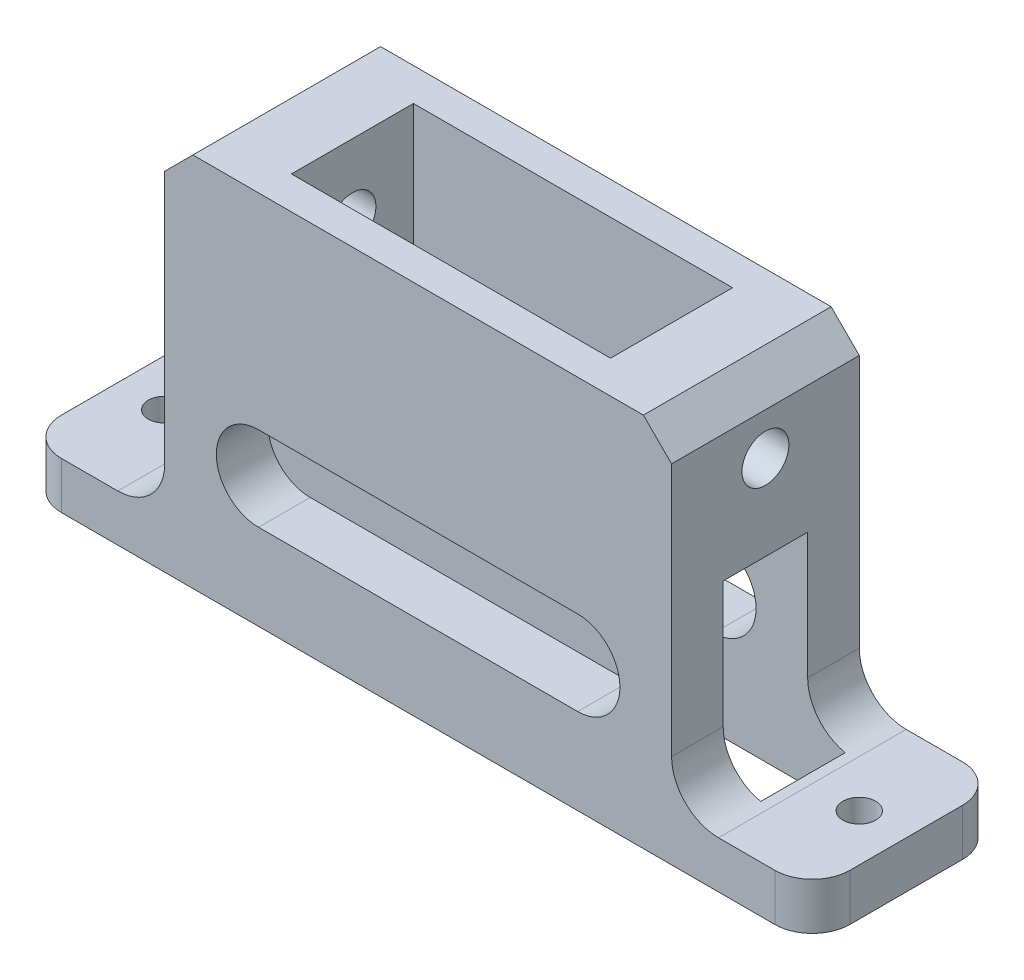
SolidWorks part; units mm, degrees
ref_plane "Front Plane" through (0, 0, 0) normal (0, 0, 1) x (1, 0, 0)
ref_plane "Top Plane" through (0, 0, 0) normal (0, 1, 0) x (1, 0, 0)
ref_plane "Right Plane" through (0, 0, 0) normal (1, 0, 0) x (0, 0, -1)
sketch "Sketch1" plane through (0, 0, 0) normal (0, 1, 0) x (1, 0, 0)
  line L1 (-27, 10) -> (27, 10)
  line L2 (-27, 10) -> (-27, -10)
  line L3 (-27, -10) -> (27, -10)
  line L4 (27, 10) -> (27, -10)
  line L5 (-27, 10) -> (27, -10) construction
  line L6 (-27, -10) -> (27, 10) construction
  point P0 (0, 0)
  dimension "D1" = 20
  dimension "D2" = 54
extrude "Boss-Extrude1" add sketch "Sketch1" along normal blind 40
sketch "Sketch4" plane through (0, 0, 0) normal (0, -1, 0) x (1, 0, 0)
  line L0 (27, -10) -> (-27, -10) construction
  line L1 (-27, 10) -> (-42, 10)
  line L2 (-27, 10) -> (-27, -10)
  line L3 (-27, -10) -> (-42, -10)
  line L4 (-42, 10) -> (-42, -10)
  line L5 (0, -11) -> (0, 11) construction
  line L6 (42, 10) -> (42, -10)
  line L7 (27, -10) -> (42, -10)
  line L8 (27, 10) -> (27, -10)
  line L9 (27, 10) -> (42, 10)
  dimension "D1" = 15
extrude "Boss-Extrude2" add sketch "Sketch4" against normal blind 5
fillet "Fillet1" radius 5 2 edges at (27, 5, 0) (-27, 5, 0)
sketch "Sketch6" plane through (0, 40, 0) normal (0, -1, 0) x (1, 0, 0)
  line L0 (17, 6.5) -> (-17, -6.5) construction
  line L1 (-17, 6.5) -> (17, 6.5)
  line L2 (-17, 6.5) -> (-17, -6.5)
  line L3 (-17, -6.5) -> (17, -6.5)
  line L4 (17, 6.5) -> (17, -6.5)
  line L5 (-27, -10) -> (-27, 10) construction
  dimension "D1" = 10
  dimension "D2" = 13
extrude "Cut-Extrude3" cut sketch "Sketch6" along normal offset from surface (26.35 mm away) 13.65 up to face at (0, 0, 0)
sketch "Sketch7" plane through (0, 0, 10) normal (0, 0, 1) x (1, 0, 0)
  line L0 (-17, 13.65) -> (17, 13.65) construction
  line L4 (-17, 18.15) -> (17, 18.15)
  line L8 (-17, 9.15) -> (17, 9.15)
  line L9 (0, 0) -> (0, 40) construction
  line L10 (-27, 40) -> (27, 40) construction
  line L11 (-17, 13.65) -> (-17, 40) construction
  line L12 (-42, 0) -> (42, 0) construction
  arc A2 (-17, 18.15) -> (-17, 9.15) centre (-17, 13.65) ccw
  arc A3 (17, 9.15) -> (17, 18.15) centre (17, 13.65) ccw
  point P2 (0, 13.65)
  dimension "D1" = 9
  dimension "D2" = 13.65
extrude "Cut-Extrude4" cut sketch "Sketch7" against normal through all
sketch "Sketch3" plane through (-27, 0, 0) normal (-1, 0, 0) x (0, 0, 1)
  line L2 (-10, 32.52) -> (10, 32.52) construction
  line L3 (-10, 40) -> (-10, 10) construction
  line L4 (10, 40) -> (10, 10) construction
  line L6 (10, 0) -> (-10, 0) construction
  line L7 (-10, 40) -> (-10, 10) construction
  line L8 (-10, 13.65) -> (-10, 32.52) construction
  circle A0 centre (0, 32.52) radius 2.5
  dimension "D1" = 5
  dimension "D2" = 13.65
  dimension "D3" = 18.87
extrude "Cut-Extrude2" cut sketch "Sketch3" against normal through all
ref_plane "Plane2" through (0, 0, -4.5) normal (0, 0, -1) x (-1, 0, 0)
sketch "Sketch8" plane through (0, 0, -4.5) normal (0, 0, -1) x (-1, 0, 0)
  line L0 (-17, 13.65) -> (17, 13.65) construction
  line L1 (-17, 27.65) -> (17, 27.65)
  line L3 (31, 13.65) -> (31, 0)
  line L4 (31, 0) -> (-31, 0)
  line L5 (-31, 0) -> (-31, 13.65)
  line L6 (42, 0) -> (-42, 0) construction
  arc A1 (-17, 27.65) -> (-31, 13.65) centre (-17, 13.65) ccw
  arc A3 (31, 13.65) -> (17, 27.65) centre (17, 13.65) ccw
  point P3 (0, 13.65)
  point P8 (0, 13.65)
  point P9 (37.6061, 0)
  point P11 (0, 0)
  point P14 (-31, 13.65)
  point P15 (-31, 13.65)
  point P16 (0, 0)
  point P17 (-31, 13.65)
  point P20 (17, 27.3)
  dimension "D1" = 14
extrude "Cut-Extrude5" cut sketch "Sketch8" against normal blind 9
sketch "Sketch9" plane through (0, 5, 0) normal (0, 1, 0) x (1, 0, 0)
  line L0 (-32, 0) -> (-42, 0) construction
  line L1 (-32, -10) -> (-32, 10) construction
  line L2 (-42, -10) -> (-42, 10) construction
  line L3 (32, 0) -> (42, 0) construction
  line L4 (32, 10) -> (32, -10) construction
  line L5 (42, 10) -> (42, -10) construction
  circle A0 centre (-37, 0) radius 1.75
  circle A1 centre (37, 0) radius 1.75
  dimension "D1" = 3.5
  dimension "D2" = 3.5
extrude "Cut-Extrude6" cut sketch "Sketch9" against normal through all
fillet "Fillet2" radius 4 4 edges at (-42, 2.5, -10) (42, 2.5, 10) (42, 2.5, -10) (-42, 2.5, 10)
chamfer "Chamfer1" distance 3 angle 45 2 edges at (27, 40, 0) (-27, 40, 0)
